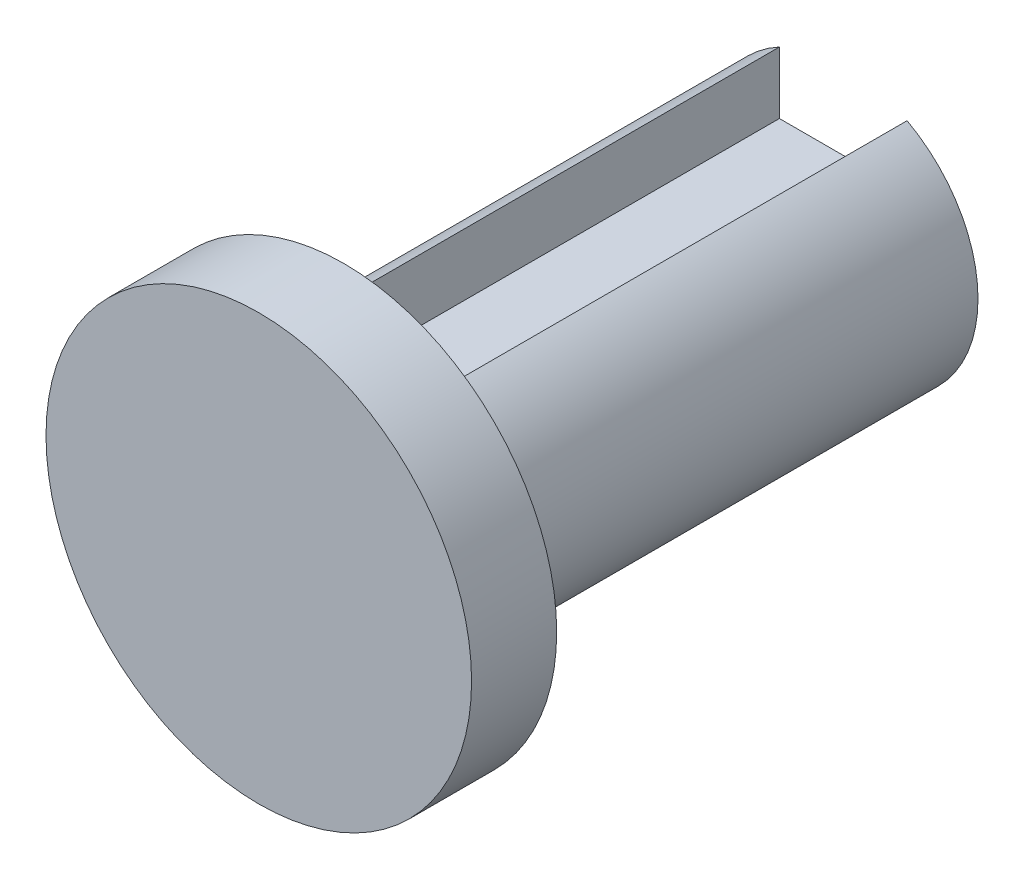
SolidWorks part; units mm, degrees
ref_plane "Front Plane" through (0, 0, 0) normal (0, 0, 1) x (1, 0, 0)
ref_plane "Top Plane" through (0, 0, 0) normal (0, 1, 0) x (1, 0, 0)
ref_plane "Right Plane" through (0, 0, 0) normal (1, 0, 0) x (0, 0, -1)
sketch "Sketch1" plane through (0, 0, 0) normal (0, 0, 1) x (1, 0, 0)
  line L0 (4.5, 4) -> (-4.5, 4)
  line L1 (4.5, 4) -> (4.5, 15)
  line L2 (4.5, 15) -> (-4.5, 15)
  line L3 (-4.5, 4) -> (-4.5, 15)
  line L4 (4.5, 4) -> (-4.5, 15) construction
  line L5 (4.5, 15) -> (-4.5, 4) construction
  circle A0 centre (0, 0) radius 9.5
  circle A1 centre (0, 0) radius 15
  point P2 (0, 9.5)
  dimension "D3" = 19
  dimension "D1" = 9
  dimension "D2" = 11
extrude "Boss-Extrude1" add sketch "Sketch1" along normal blind 6 contours A1
extrude "Boss-Extrude2" add sketch "Sketch1<3>" against normal blind 35.2 contours L3 A0 L1 L0 region at (0, -1.2798, 0)
sketch "Sketch1<3>" plane through (0, 0, 0) normal (0, 0, 1) x (1, 0, 0) same geometry as "Sketch1"
equation "\"shaftDiam\" = 20mm"
equation "\"keyW\" = 8mm"
equation "\"keyL\" = 10mm"
equation "\"clearance\" = 1mm"
equation "\"handleShaftLen\" = 60mm"
equation "\"panelH\" = 80mm"
equation "\"panelW\" = 110mm"
equation "\"D1@Sketch1\" = \"keyW\" + \"clearance\""
equation "\"D2@Sketch1\"= \"keyL\" + \"clearance\""
equation "\"D3@Sketch1\"=\"shaftDiam\"-\"clearance\""
equation "\"D1@Boss-Extrude1\"=\"handleShaftLen\"/10"
equation "\"D1@Boss-Extrude2\"=3*\"handleShaftLen\"/8+.5in"
